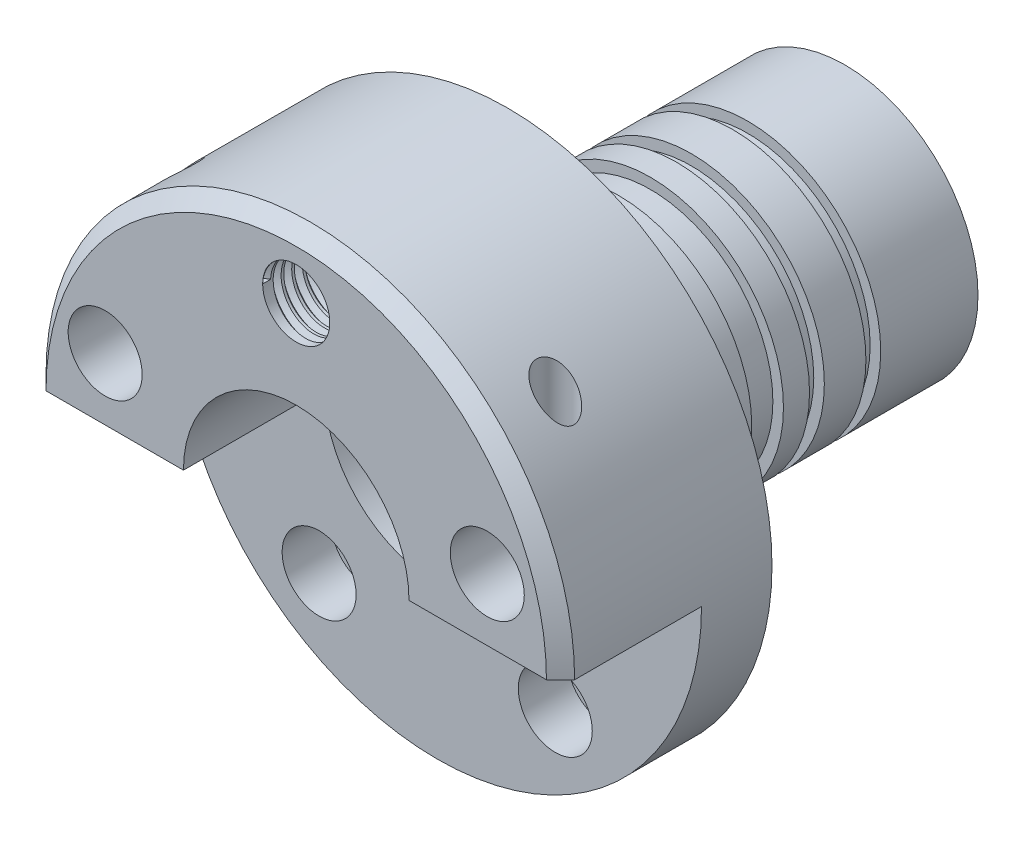
SolidWorks part; units mm, degrees
ref_plane "Front Plane" through (0, 0, 0) normal (0, 0, 1) x (1, 0, 0)
ref_plane "Top Plane" through (0, 0, 0) normal (0, 1, 0) x (1, 0, 0)
ref_plane "Right Plane" through (0, 0, 0) normal (1, 0, 0) x (0, 0, -1)
sketch "Sketch1" plane through (0, 0, 0) normal (0, 0, 1) x (1, 0, 0)
  circle A0 centre (0, 0) radius 16
  circle A1 centre (0, 0) radius 18.875
  dimension "D1" = 32
  dimension "D2" = 37.75
extrude "Boss-Extrude1" add sketch "Sketch1" along normal blind 47.85
sketch "Sketch2" plane through (0, 0, 47.85) normal (0, 0, 1) x (1, 0, 0)
  circle A0 centre (0, 0) radius 37.5
  dimension "D1" = 75
extrude "Boss-Extrude2" add sketch "Sketch2" along normal blind 30
sketch "Sketch3" plane through (0, 0, 47.85) normal (0, 0, -1) x (-1, 0, 0)
  circle A0 centre (0, 0) radius 16
  circle A1 centre (0, 0) radius 16 construction
extrude "Cut-Extrude1" cut sketch "Sketch3" against normal blind 47.85
sketch "Sketch4" plane through (0, 0, 0) normal (0, 1, 0) x (1, 0, 0)
  line L0 (-37.5, -57.85) -> (37.5, -57.85) construction
  line L1 (-37.5, -47.85) -> (-37.5, -77.85) construction
  line L2 (37.5, -77.85) -> (37.5, -47.85) construction
  line L3 (37.5, -47.85) -> (-37.5, -47.85) construction
  line L4 (-37.5, -77.85) -> (37.5, -77.85) construction
  line L5 (-37.5, -57.85) -> (37.5, -57.85)
  line L6 (-37.5, -57.85) -> (-37.5, -77.85)
  line L7 (-37.5, -77.85) -> (37.5, -77.85)
  line L8 (37.5, -57.85) -> (37.5, -77.85)
  dimension "D1" = 10
extrude "Cut-Extrude2" cut sketch "Sketch4" against normal blind 47.85
sketch "Sketch5" plane through (0, 0, 0) normal (0, -1, 0) x (-1, 0, 0)
  line L0 (37.5, -77.85) -> (16, -57.85) construction
  line L1 (-16, -77.85) -> (-37.5, -57.85) construction
  circle A0 centre (26.75, -67.85) radius 2.65
  circle A1 centre (-26.75, -67.85) radius 2.65
  dimension "D1" = 5.3
  dimension "D2" = 5.3
extrude "Cut-Extrude3" cut sketch "Sketch5" against normal blind 47.85
sketch "Sketch11" plane through (0, 0, 77.85) normal (0, 0, 1) x (1, 0, 0)
  line L0 (0, 0) -> (0, 37.5) construction
  arc A0 (37.5, 0) -> (-37.5, 0) centre (0, 0) ccw construction
  circle A1 centre (0, 0) radius 28.5 construction
  circle A2 centre (0, 28.5) radius 1
  point P19 (0, 0)
  dimension "D1" = 57
  dimension "D2" = 2
extrude "Cut-Extrude4" cut sketch "Sketch11" against normal up to surface (30 mm away) up to face at (18.875, 0, 47.85)
thread "Thread1" pitch 1 method cut profile "Thread Profile1" start angle 0, offset 0, length 5, pitch 1, diameter 5.3
ref_plane "Plane1" through (-24.1, 0, 67.85) normal (0, 0, 1) x (1, 0, 0)
sketch "Thread Profile1" plane through (-24.1, 0, 67.85) normal (0, 0, 1) x (1, 0, 0)
  line L0 (0, 0) -> (0, 1) construction
  line L1 (0, 0) -> (0.5413, 0.3125)
  line L2 (0.5413, 0.3125) -> (0.5413, 0.4375)
  line L3 (0.5413, 0.4375) -> (0, 0.75)
  line L4 (0.5413, 0.375) -> (0, 0.375) construction
  line L11 (0, 0) -> (0, 0.75)
  point P2 (0, 0)
  dimension "Pitch" = 1
  dimension "Profile_Angle" = 60
  dimension "Profile_Land" = 0.125
  dimension "Profile_Height" = 0.5413
thread "Thread2" pitch 1 method cut profile "Thread Profile2" start angle 0, offset 0, length 5, pitch 1, diameter 5.3
ref_plane "Plane2" through (29.4, 0, 67.85) normal (0, 0, 1) x (1, 0, 0)
sketch "Thread Profile2" plane through (29.4, 0, 67.85) normal (0, 0, 1) x (1, 0, 0)
  line L0 (0, 0) -> (0, 1) construction
  line L1 (0, 0) -> (0.5413, 0.3125)
  line L2 (0.5413, 0.3125) -> (0.5413, 0.4375)
  line L3 (0.5413, 0.4375) -> (0, 0.75)
  line L4 (0.5413, 0.375) -> (0, 0.375) construction
  line L11 (0, 0) -> (0, 0.75)
  point P2 (0, 0)
  dimension "Pitch" = 1
  dimension "Profile_Angle" = 60
  dimension "Profile_Land" = 0.125
  dimension "Profile_Height" = 0.5413
sketch "Sketch12" plane through (0, 0, 77.85) normal (0, 0, 1) x (1, 0, 0)
  circle A0 centre (0, 28.5) radius 4.7625
  point P16 (0, 0)
  dimension "D1" = 9.525
extrude "Cut-Extrude5" cut sketch "Sketch12" against normal blind 8
sketch "Sketch13" plane through (0, 0, 0) normal (1, 0, 0) x (0, 0, -1)
  line L0 (0, 0) -> (-47.85, 0) construction
  line L1 (0, -18.875) -> (0, 18.875) construction
  line L2 (-47.85, -37.5) -> (-47.85, 37.5) construction
  line L3 (-14.85, 0) -> (-14.85, 18.875) construction
  line L4 (0, 18.875) -> (-47.85, 18.875) construction
  line L5 (-22.85, 0) -> (-22.85, 18.875) construction
  line L6 (-35.85, 0) -> (-35.85, 18.875) construction
  line L7 (-39.85, 0) -> (-39.85, 18.875) construction
  line L8 (-47.85, -18.875) -> (-47.85, 18.875) construction
  line L10 (-29.85, 18.475) -> (-29.85, 0) construction
  line L11 (-47.85, -18.875) -> (0, -18.875) construction
  line L12 (-15.9, 17.375) -> (-47.85, 17.375) construction
  line L13 (-15.9, 20.375) -> (-13.8, 20.375)
  line L14 (-15.9, 20.375) -> (-15.9, 17.375)
  line L15 (-15.9, 17.375) -> (-13.8, 17.375)
  line L16 (-13.8, 20.375) -> (-13.8, 17.375)
  line L17 (-15.9, 20.375) -> (-13.8, 17.375) construction
  line L18 (-15.9, 17.375) -> (-13.8, 20.375) construction
  line L19 (0, 0) -> (0, 17.875) construction
  line L20 (-23.9, 20.375) -> (-21.8, 20.375)
  line L21 (-23.9, 20.375) -> (-23.9, 17.375)
  line L22 (-23.9, 17.375) -> (-21.8, 17.375)
  line L23 (-21.8, 20.375) -> (-21.8, 17.375)
  line L24 (-23.9, 20.375) -> (-21.8, 17.375) construction
  line L25 (-23.9, 17.375) -> (-21.8, 20.375) construction
  line L26 (-36.9, 20.375) -> (-34.8, 20.375)
  line L27 (-36.9, 20.375) -> (-36.9, 17.375)
  line L28 (-36.9, 17.375) -> (-34.8, 17.375)
  line L29 (-34.8, 20.375) -> (-34.8, 17.375)
  line L30 (-36.9, 20.375) -> (-34.8, 17.375) construction
  line L31 (-36.9, 17.375) -> (-34.8, 20.375) construction
  line L32 (-40.9, 20.375) -> (-38.8, 20.375)
  line L33 (-40.9, 20.375) -> (-40.9, 17.375)
  line L34 (-40.9, 17.375) -> (-38.8, 17.375)
  line L35 (-38.8, 20.375) -> (-38.8, 17.375)
  line L36 (-40.9, 20.375) -> (-38.8, 17.375) construction
  line L37 (-40.9, 17.375) -> (-38.8, 20.375) construction
  line L38 (-16.9262, 17.375) -> (-16.9262, 19.375) construction
  line L40 (-32.1, 19.575) -> (-27.6, 19.575)
  line L41 (-32.1, 19.575) -> (-32.1, 17.375)
  line L42 (-32.1, 17.375) -> (-27.6, 17.375)
  line L43 (-27.6, 19.575) -> (-27.6, 17.375)
  line L44 (-32.1, 19.575) -> (-27.6, 17.375) construction
  line L45 (-32.1, 17.375) -> (-27.6, 19.575) construction
  point P21 (-29.85, 9.2375)
  dimension "D1" = 8
  dimension "D2" = 12
  dimension "D3" = 25
  dimension "D4" = 33
  dimension "D5" = 1.5
  dimension "D6" = 2.1
  dimension "D7" = 2.1
  dimension "D8" = 2.1
  dimension "D9" = 2.1
  dimension "D10" = 2
  dimension "D11" = 4.5
  dimension "D12" = 18
revolve "Cut-Revolve1" cut sketch "Sketch13" angle 360 about L0
sketch "Sketch18" plane through (0, 0, 77.85) normal (0, 0, 1) x (1, 0, 0)
  circle A0 centre (0, 28.5) radius 3.125 construction
  circle A1 centre (27.1051, 8.807) radius 3.125
  circle A2 centre (16.7519, -23.057) radius 3.125
  circle A3 centre (-16.7519, -23.057) radius 3.125
  circle A4 centre (-27.1051, 8.807) radius 3.125
  point P13 (0, 0)
  dimension "D1" = 6.25
  dimension "D2" = 5
extrude "Cut-Extrude8" cut sketch "Sketch18" against normal up to surface (30 mm away) up to face at (1, 28.5, 47.85)
sketch "Sketch19" plane through (0, 0, 77.85) normal (0, 0, 1) x (1, 0, 0)
  circle A0 centre (0, 28.5) radius 5.25 construction
  circle A1 centre (27.1051, 8.807) radius 5.25
  circle A2 centre (16.7519, -23.057) radius 5.25
  circle A3 centre (-16.7519, -23.057) radius 5.25
  circle A4 centre (-27.1051, 8.807) radius 5.25
  point P13 (0, 0)
  dimension "D1" = 10.5
  dimension "D2" = 5
extrude "Cut-Extrude9" cut sketch "Sketch19" against normal blind 27
thread "Thread3" pitch 1.5 method cut profile "Thread Profile3" start angle 0, offset 0, length 8, pitch 1.5, diameter 9.525
ref_plane "Plane3" through (-4.7625, 28.5, 77.85) normal (0, -1, 0) x (-1, 0, 0)
sketch "Thread Profile3" plane through (-4.7625, 28.5, 77.85) normal (0, -1, 0) x (-1, 0, 0)
  line L0 (0, 0) -> (0, 1.5) construction
  line L1 (0, 0) -> (0.8119, 0.4687)
  line L2 (0.8119, 0.4687) -> (0.8119, 0.6562)
  line L3 (0.8119, 0.6562) -> (0, 1.125)
  line L4 (0.8119, 0.5625) -> (0, 0.5625) construction
  line L11 (0, 0) -> (0, 1.125)
  point P2 (0, 0)
  dimension "Pitch" = 1.5
  dimension "Profile_Angle" = 60
  dimension "Profile_Land" = 0.1875
  dimension "Profile_Height" = 0.8119
ref_plane "Plane4" through (0, 38, 0) normal (0, 1, 0) x (1, 0, 0)
sketch "Sketch27" plane through (0, 0, 47.85) normal (0, 0, -1) x (-1, 0, 0)
  line L0 (0, 33.125) -> (0, 34.725) construction
  circle A0 centre (0, 28.5) radius 4.625 construction
  circle A1 centre (0, 28.5) radius 6.225
  dimension "D1" = 9.25
  dimension "D2" = 1.6
extrude "Cut-Extrude12" cut sketch "Sketch27" against normal blind 0.8
chamfer "Chamfer1" distance 2 angle 45 1 edges at (0, 37.5, 77.85)
